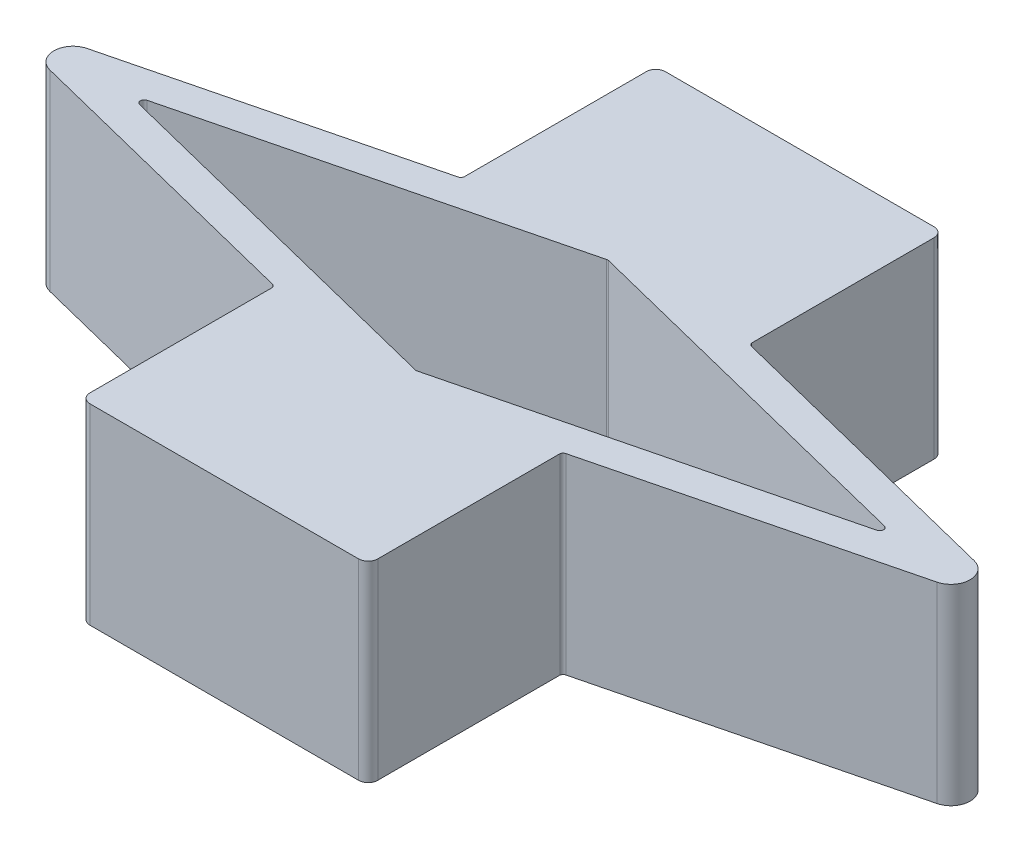
SolidWorks part; units mm, degrees
ref_plane "Front Plane" through (0, 0, 0) normal (0, 0, 1) x (1, 0, 0)
ref_plane "Top Plane" through (0, 0, 0) normal (0, 1, 0) x (1, 0, 0)
ref_plane "Right Plane" through (0, 0, 0) normal (1, 0, 0) x (0, 0, -1)
sketch "Sketch1" plane through (0, 0, 0) normal (0, 1, 0) x (1, 0, 0)
  line L0 (0, 15) -> (-20, 10)
  line L1 (-7.5, -5) -> (7.5, -5)
  line L2 (-7.5, -5) -> (-7.5, 5)
  line L3 (-7.5, 5) -> (7.5, 5)
  line L4 (7.5, -5) -> (7.5, 5)
  line L5 (-7.5, -5) -> (7.5, 5) construction
  line L6 (-7.5, 5) -> (7.5, -5) construction
  line L7 (-7.5, 15) -> (7.5, 15)
  line L8 (-7.5, 15) -> (-7.5, 25)
  line L9 (-7.5, 25) -> (7.5, 25)
  line L10 (7.5, 15) -> (7.5, 25)
  line L11 (-7.5, 15) -> (7.5, 25) construction
  line L12 (-7.5, 25) -> (7.5, 15) construction
  line L13 (-20, 10) -> (0, 5)
  line L14 (-7.0093, 15) -> (-27.0093, 10)
  line L15 (-27.0093, 10) -> (-7.0093, 5)
  line L16 (0, 20) -> (0, 0) construction
  point P0 (0, 0)
  point P6 (0, 20)
  point P17 (0, 10)
  dimension "D1" = 10
  dimension "D2" = 15
  dimension "D3" = 10
  dimension "D4" = 15
  dimension "D5" = 20
  dimension "D6" = 40
  dimension "D7" = 1.7
extrude "Boss-Extrude2" add sketch "Sketch1" along normal blind 10 contours L7 L10 L9 L8 | L1 L4 L3 L2 region at (0, 0, -20) region at (0, 0, 0)
extrude "Boss-Extrude3" add sketch "Sketch1<4>" along normal blind 10 contours L14 L15 L3 L13 L0 L7 region at (-10.0699, 0, -12.7794)
sketch "Sketch1<4>" plane through (0, 0, 0) normal (0, 1, 0) x (1, 0, 0) same geometry as "Sketch1"
ref_plane "Plane1" through (0, 0, 0) normal (-1, 0, 0) x (0, 0, 1)
mirror "Mirror1" about plane through (0, 0, 0) normal (-1, 0, 0) of "Boss-Extrude3"
fillet "Fillet1" radius 0.2 8 edges at (7.0093, 5, -5) (7.0093, 5, -15) (-7.0093, 5, -15) (-7.0093, 5, -5) (0, 5, -5) (20, 5, -10) (0, 5, -15) (-20, 5, -10)
fillet "Fillet2" radius 1 2 edges at (27.0093, 5, -10) (-27.0093, 5, -10)
fillet "Fillet3" radius 0.5 4 edges at (7.5, 5, -25) (-7.5, 5, -25) (7.5, 5, 5) (-7.5, 5, 5)
